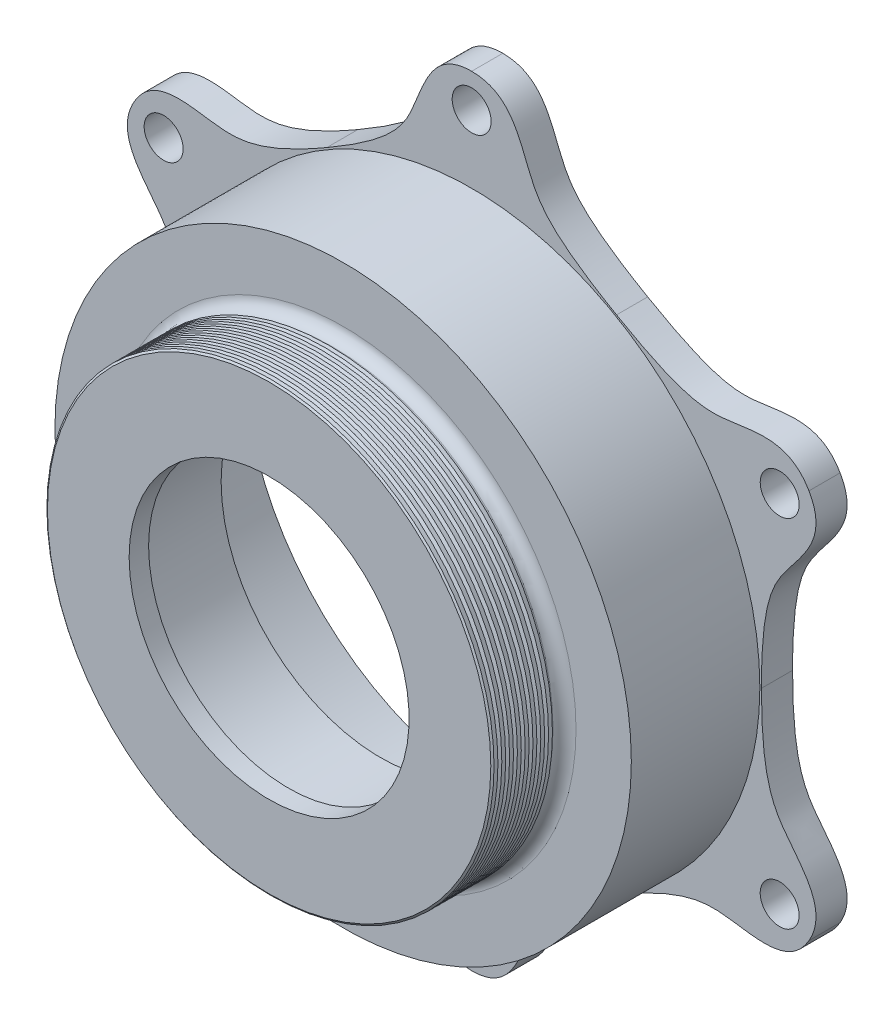
SolidWorks part; units mm, degrees
other "DetailItem1"
material "6061-T6 (SS)"
ref_plane "Front Plane" through (0, 0, 0) normal (0, 0, 1) x (1, 0, 0)
ref_plane "Top Plane" through (0, 0, 0) normal (0, 1, 0) x (1, 0, 0)
ref_plane "Right Plane" through (0, 0, 0) normal (1, 0, 0) x (0, 0, -1)
ref_axis "Axis1" through (0, 0, -58.1544) along (0, 0, 1)
sketch "Sketch1" plane through (0, 0, 0) normal (1, 0, 0) x (0, 0, -1)
  line L0 (0, 0) -> (-50000, 0) construction
  line L1 (-33.02, 22.825) -> (-29.845, 22.825)
  line L2 (-29.845, 22.825) -> (-29.845, 26)
  line L3 (0, 46.99) -> (-20.955, 46.99)
  line L4 (5.08, 42.2275) -> (5.08, 63.5)
  line L5 (5.08, 63.5) -> (0, 63.5)
  line L6 (0, 63.5) -> (0, 46.99)
  line L7 (-33.02, 36.449) -> (-20.955, 36.449)
  line L8 (-20.955, 36.449) -> (-20.955, 46.99)
  line L9 (-23, 77.2973) -> (-23, -14.4513) construction
  line L10 (-29.845, 26) -> (-14.845, 26)
  line L11 (-14.845, 26) -> (-14.845, 42.2275)
  line L12 (-20.955, 46.99) -> (-20.955, 26) construction
  line L13 (-14.845, 42.2275) -> (5.08, 42.2275)
  line L14 (-33.02, 36.449) -> (-33.02, 30.099)
  line L16 (-33.02, 30.099) -> (-33.02, 22.825)
  dimension "D2" = 3.175
  dimension "D3" = 63.5
  dimension "D4" = 20.955
  dimension "D5" = 5.08
  dimension "D6" = 3.175
  dimension "D7" = 46.99
  dimension "D8" = 26
  dimension "D9" = 38.1
  dimension "D10" = 4.7625
  dimension "D11" = 6.35
  dimension "D13" = 72.898
  dimension "D14" = 23
  dimension "D15" = 15
revolve "Revolve1" add sketch "Sketch1" angle 360 about L0
sketch "Sketch2" plane through (0, 0, 0) normal (0, 0, 1) x (1, 0, 0)
  line L0 (0, 0) -> (0, 57.9882) construction
  circle A0 centre (0, 57.9882) radius 3.175
  dimension "D1" = 6.35
  dimension "D2" = 57.9882
extrude "Extrude1" cut sketch "Sketch2" against normal up to next
pattern_circular "CirPattern1" count 6 over 360 about axis through (0, 0, -58.1544) along (0, 0, 1) of "Extrude1"
sketch "Sketch3" plane through (0, 0, 0) normal (1, 0, 0) x (0, 0, -1)
  line L0 (-32.7998, 36.449) -> (-33.1661, 35.941)
  line L2 (-33.1661, 35.941) -> (-33.1661, 36.8649)
  line L3 (-33.1661, 36.8649) -> (-31.8961, 36.8649)
  line L4 (-32.7998, 36.449) -> (-32.1648, 36.449)
  line L5 (-33.02, 36.449) -> (-20.955, 36.449) construction
  line L6 (-32.1648, 36.449) -> (-32.5311, 35.941)
  line L7 (-32.5311, 35.941) -> (-31.8961, 35.941)
  line L8 (-31.8961, 35.941) -> (-31.8961, 36.8649)
  line L9 (-20.955, 36.449) -> (-33.02, 36.449) construction
  dimension "D1" = 1.27
  dimension "D2" = 0.508
revolve "Cut-Revolve1" cut sketch "Sketch3" angle 360 about axis through (0, 0, -58.1544) along (0, 0, 1)
pattern_linear "LPattern1" count 8 spacing 1.27 along (0, 0, -1) of "Cut-Revolve1"
sketch "Sketch5" plane through (0, 0, 0) normal (1, 0, 0) x (0, 0, -1)
  line L0 (-20.955, 36.449) -> (-23.0061, 36.449) construction
  line L1 (-20.955, 46.99) -> (-20.955, -46.99) construction
  line L2 (-20.955, 36.449) -> (-23.0061, 36.449)
  line L3 (-20.955, 36.449) -> (-20.955, 35.941)
  line L4 (-23.0061, 36.449) -> (-23.0061, -36.449) construction
  line L5 (-23.0061, 36.449) -> (-23.0061, 35.941)
  line L6 (-23.0061, 35.941) -> (-20.955, 35.941)
  line L7 (-23.0061, 35.941) -> (-23.6411, 35.941) construction
revolve "Cut-Revolve2" cut sketch "Sketch5" angle 360 about axis through (0, 0, -58.1544) along (0, 0, 1)
fillet "Fillet1" radius 2.032 1 edges at (-35.941, 0, 20.955)
fillet "Fillet3" radius 0.508 1 edges at (-35.941, 0, 23.6411)
sketch "Sketch4" plane through (0, 0, 0) normal (0, 0, 1) x (1, 0, 0)
  line L0 (0, 0) -> (51.1012, 88.5099) construction
  line L1 (0, 0) -> (0, 86.0554) construction
  line L2 (0, 0) -> (78.6704, 45.4204) construction
  line L3 (25.6183, 39.7619) -> (21.6257, 42.0671) construction
  circle A0 centre (0, 0) radius 63.5 construction
  arc A1 (54.9926, 31.75) -> (0, 63.5) centre (0, 0) ccw
  circle A3 centre (0, 0) radius 46.99 construction
  spline S0 degree 3 poles (0, 63.5) (6.0754, 63.5) (9.0354, 53.5896) (12.7049, 47.2175) (23.622, 40.9145) knots 0 0 0 0 0.515622 1 1 1 1
  spline S1 degree 3 poles (54.9926, 31.75) (51.9549, 37.0115) (41.8923, 34.6197) (34.5391, 34.6115) (23.622, 40.9145) knots 0 0 0 0 0.515622 1 1 1 1
  point P6 (23.495, 40.6945)
  dimension "D1" = 30
  dimension "D2" = 0.254
extrude "Cut-Extrude1" cut sketch "Sketch4" against normal through all
pattern_circular "CirPattern2" count 6 over 360 about axis through (0, 0, -58.1544) along (0, 0, 1) of "Cut-Extrude1"
fillet "Fillet2" radius 1.5875 1 edges at (-42.2275, 0, 14.845)
